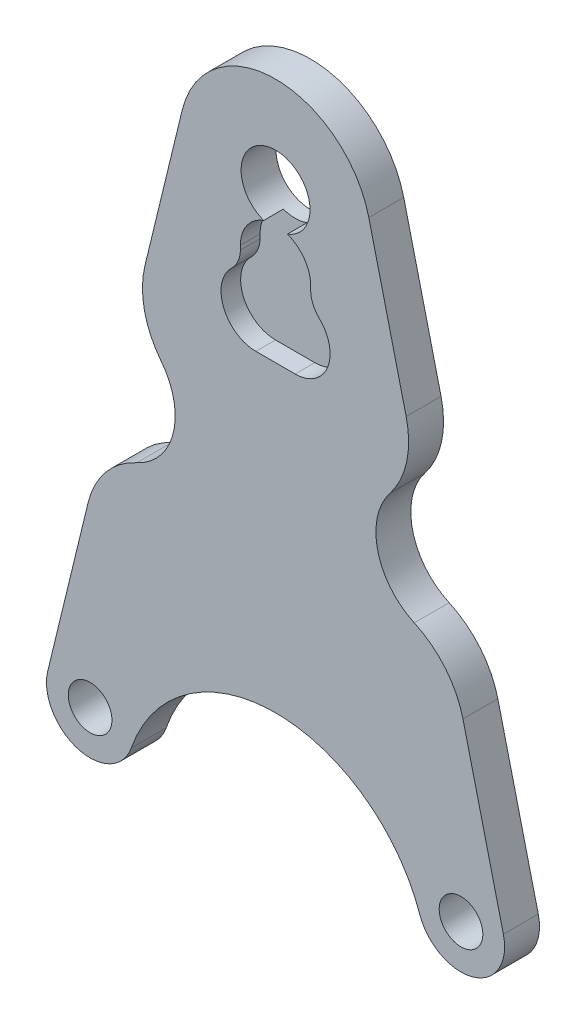
SolidWorks part; units mm, degrees
ref_plane "Спереди" through (0, 0, 0) normal (0, 0, 1) x (1, 0, 0)
ref_plane "Сверху" through (0, 0, 0) normal (0, 1, 0) x (1, 0, 0)
ref_plane "Справа" through (0, 0, 0) normal (1, 0, 0) x (0, 0, -1)
sketch "Эскиз1" plane through (0, 0, 0) normal (0, 0, 1) x (1, 0, 0)
  line L0 (0, 20) -> (0, -181.3933) construction
  line L6 (-21.3772, 5.1978) -> (-52.2169, -121.6374)
  line L8 (21.3772, 5.1978) -> (52.2169, -121.6374)
  circle A0 centre (0, 0) radius 7.9
  circle A1 centre (-42.5, -124) radius 5
  arc A2 (-21.3772, 5.1978) -> (21.3772, 5.1978) centre (0, 0) cw
  arc A3 (-52.2169, -121.6374) -> (-33.0556, -127.2867) centre (-42.5, -124) ccw
  circle A5 centre (42.5, -124) radius 5
  arc A6 (52.2169, -121.6374) -> (33.0556, -127.2867) centre (42.5, -124) cw
  arc A8 (-33.0556, -127.2867) -> (33.0556, -127.2867) centre (0, -138.7902) cw
  point P8 (0, -134)
  point P19 (0, -134)
  dimension "D1" = 15.8
  dimension "D4" = 22
  dimension "D6" = 10
  dimension "D5" = 10
  dimension "D7" = 35
  dimension "D2" = 85
  dimension "D3" = 124
extrude "Бобышка-Вытянуть1" add sketch "Эскиз1" along normal blind 8
sketch "Эскиз2" plane through (0, 0, 8) normal (0, 0, 1) x (1, 0, 0)
  line L0 (0, -16) -> (0, -54) construction
  line L3 (4.5, -34.3) -> (-4.5, -34.3)
  line L4 (0, 0) -> (0, -65.5898) construction
  line L5 (-8.05, -16) -> (-8.05, -15)
  line L6 (8.05, -16) -> (8.05, -15)
  arc A8 (8.05, -16) -> (10.0356, -20.5244) centre (14.4986, -15.8679) ccw
  arc A10 (10.0356, -20.5244) -> (4.5, -34.3) centre (4.5, -26.3) cw
  arc A12 (-10.0356, -20.5244) -> (-4.5, -34.3) centre (-4.5, -26.3) ccw
  arc A13 (-8.05, -16) -> (-10.0356, -20.5244) centre (-14.4986, -15.8679) cw
  arc A14 (-8.05, -15) -> (8.05, -15) centre (0, -15) cw
  point P8 (0, -35)
  point P20 (0, -34.3)
  dimension "D1" = 16
  dimension "D2" = 15.8679
  dimension "D4" = 16.1
  dimension "D6" = 15.8679
  dimension "D7" = 38
  dimension "D8" = 6.45
  dimension "D9" = 8
  dimension "D10" = 8
  dimension "D3" = 9
  dimension "D5" = 26.3
  dimension "D11" = 1
extrude "Вырез-Вытянуть1" cut sketch "Эскиз2" against normal blind 4.5
sketch "Эскиз3" plane through (0, 0, 8) normal (0, 0, 1) x (1, 0, 0)
  line L0 (0, 0) -> (0, -88.8714) construction
  circle A0 centre (-38, -56.3915) radius 15
  circle A1 centre (38, -56.3915) radius 15
  circle A2 centre (0, -26) radius 7.5 construction
  dimension "D1" = 68
  dimension "D2" = 30
  dimension "D4" = 15
  dimension "D3" = 38
  dimension "D5" = 26
extrude "Вырез-Вытянуть2" cut sketch "Эскиз3" against normal through all
fillet "Скругление1" radius 20 4 edges at (39.9682, -71.2618, 4) (32.9207, -42.2776, 4) (-39.9682, -71.2618, 4) (-32.9207, -42.2776, 4)
